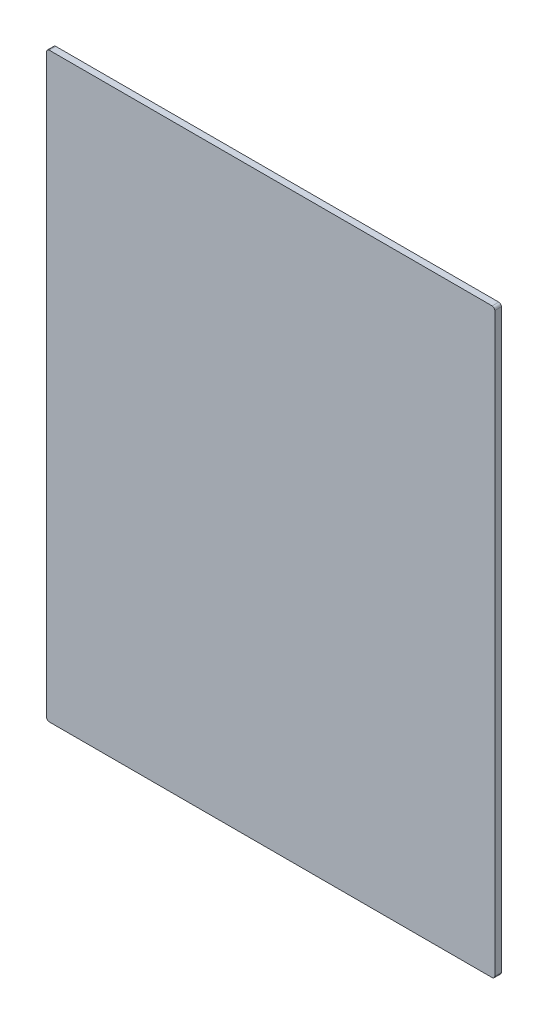
SolidWorks part; units mm, degrees
material "Plain Carbon Steel"
ref_plane "Front Plane" through (0, 0, 0) normal (0, 0, 1) x (1, 0, 0)
ref_plane "Top Plane" through (0, 0, 0) normal (0, 1, 0) x (1, 0, 0)
ref_plane "Right Plane" through (0, 0, 0) normal (1, 0, 0) x (0, 0, -1)
sketch "Sketch1" plane through (0, 0, 0) normal (0, 0, 1) x (1, 0, 0)
  line L0 (355.6, -484.2272) -> (0, 0) construction
  line L1 (0, 0) -> (0, 38.1) construction
  line L2 (393.7, -522.3669) -> (-38.1, -522.3669)
  line L3 (393.7, -522.3669) -> (393.7, 38.1)
  line L4 (393.7, 38.1) -> (-38.1, 38.1)
  line L5 (-38.1, -522.3669) -> (-38.1, 38.1)
  line L6 (393.7, -522.3669) -> (-38.1, 38.1) construction
  line L7 (393.7, 38.1) -> (-38.1, -522.3669) construction
  line L8 (-25.4, -21.4312) -> (-25.4, 21.4312) construction
  line L9 (0, 0) -> (-38.1, 0) construction
  point P4 (177.8, -242.1334)
  dimension "D1" = 12.7
extrude "Boss-Extrude1" add sketch "Sketch1" along normal blind 6.35
fillet "Fillet1" radius 2.54 4 edges at (393.7, 38.1, 3.175) (393.7, -522.3669, 3.175) (-38.1, -522.3669, 3.175) (-38.1, 38.1, 3.175)
